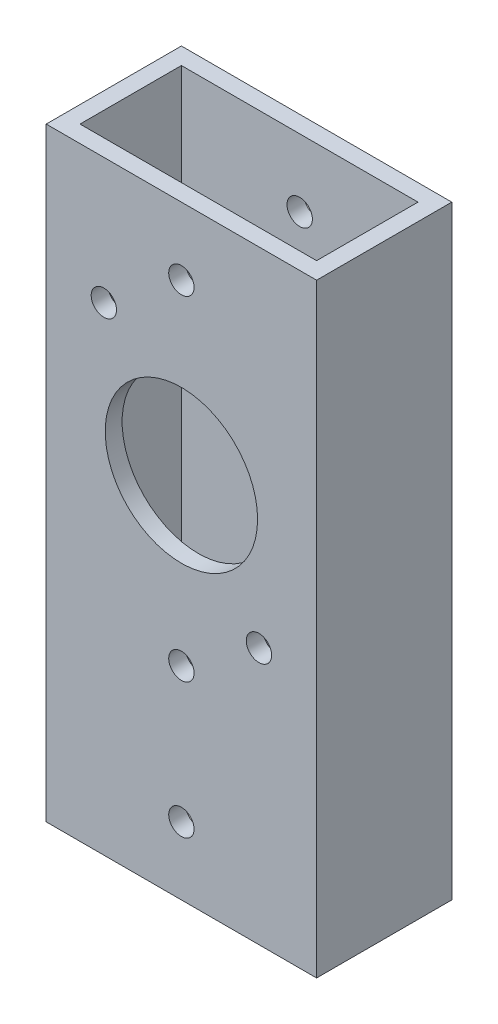
SolidWorks part; units mm, degrees
material "6063-T1"
ref_plane "Front Plane" through (0, 0, 0) normal (0, 0, 1) x (1, 0, 0)
ref_plane "Top Plane" through (0, 0, 0) normal (0, 1, 0) x (1, 0, 0)
ref_plane "Right Plane" through (0, 0, 0) normal (1, 0, 0) x (0, 0, -1)
sketch "Sketch1" plane through (0, 0, 0) normal (0, 0, 1) x (1, 0, 0)
  line L1 (-25.4, 56.769) -> (25.4, 56.769)
  line L2 (-25.4, 56.769) -> (-25.4, -56.769)
  line L3 (-25.4, -56.769) -> (25.4, -56.769)
  line L4 (25.4, 56.769) -> (25.4, -56.769)
  line L5 (-25.4, 56.769) -> (25.4, -56.769) construction
  line L6 (-25.4, -56.769) -> (25.4, 56.769) construction
  point P0 (0, 0)
  dimension "D1" = 50.8
  dimension "D2" = 113.538
extrude "Boss-Extrude1" add sketch "Sketch1" along normal blind 25.4
shell "Shell1" thickness 3.175 removed face at (0, -56.769, 12.7) removed face at (0, 56.769, 12.7)
sketch "Sketch2" plane through (0, 0, 25.4) normal (0, 0, 1) x (1, 0, 0)
  line L0 (25.4, 56.769) -> (-25.4, 56.769) construction
  circle A0 centre (0, 12.319) radius 14.3129
  dimension "D1" = 28.6258
  dimension "D2" = 44.45
extrude "Cut-Extrude1" cut sketch "Sketch2" against normal up to vertex (25.4 mm away) up to point (0, 0, 0)
sketch "Sketch3" plane through (0, 0, 25.4) normal (0, 0, 1) x (1, 0, 0)
  line L0 (25.4, 56.769) -> (-25.4, 56.769) construction
  line L1 (-25.4, -56.769) -> (25.4, -56.769) construction
  line L2 (0, 56.769) -> (0, -56.769) construction
  line L3 (-14.5688, 33.1255) -> (14.5688, -8.4875) construction
  circle A0 centre (0, 44.069) radius 2.3812
  circle A1 centre (0, -18.669) radius 2.3813
  circle A2 centre (0, -44.069) radius 2.3812
  circle A3 centre (0, 12.319) radius 25.4 construction
  circle A4 centre (-14.5688, 33.1255) radius 2.3812
  circle A5 centre (14.5688, -8.4875) radius 2.3813
  dimension "D4" = 4.7625
  dimension "D5" = 4.7625
  dimension "D6" = 4.7625
  dimension "D7" = 50.8
  dimension "D9" = 4.7625
  dimension "D10" = 4.7625
  dimension "D1" = 12.7
  dimension "D2" = 12.7
  dimension "D3" = 38.1
  dimension "D8" = 35
extrude "Cut-Extrude2" cut sketch "Sketch3" against normal through all
